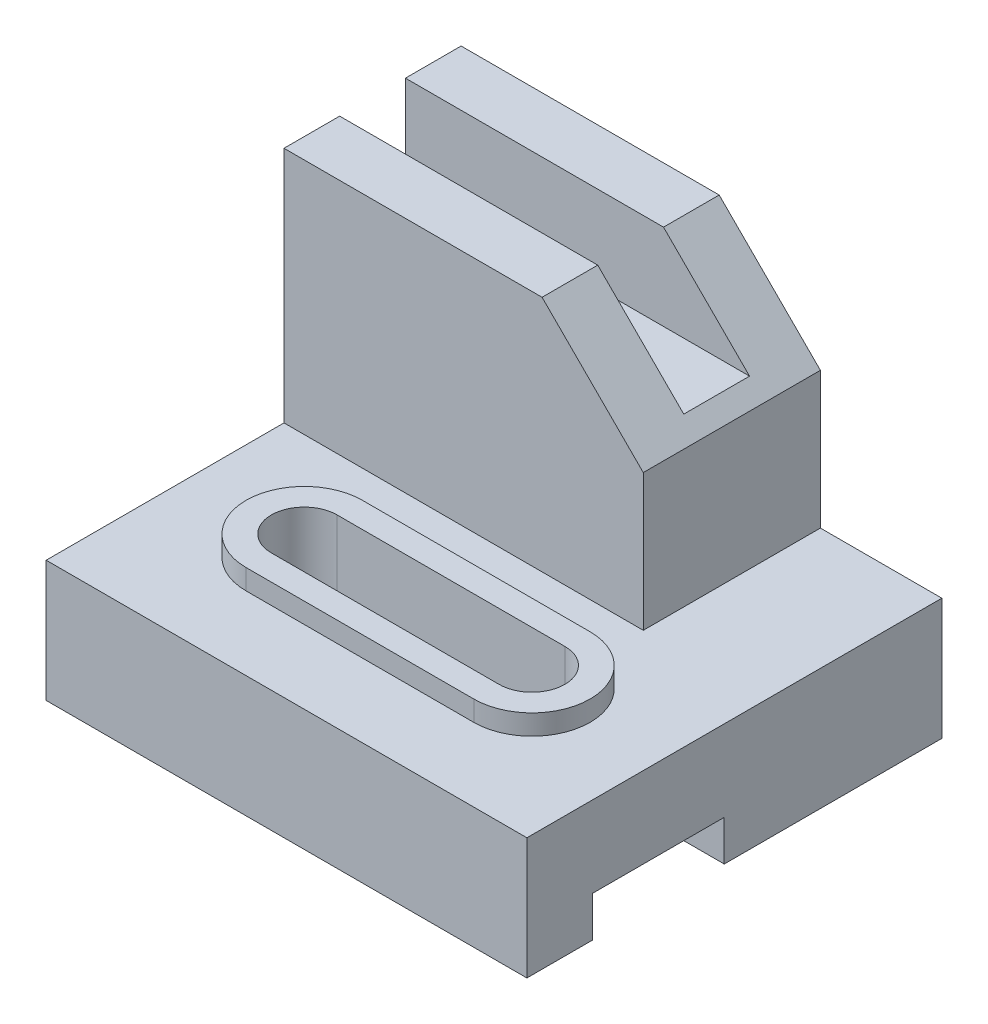
SolidWorks part; units mm, degrees
ref_plane "Front Plane" through (0, 0, 0) normal (0, 0, 1) x (1, 0, 0)
ref_plane "Top Plane" through (0, 0, 0) normal (0, 1, 0) x (1, 0, 0)
ref_plane "Right Plane" through (0, 0, 0) normal (1, 0, 0) x (0, 0, -1)
sketch "Sketch1" plane through (0, 0, 0) normal (0, 1, 0) x (1, 0, 0)
  line L0 (25, 26) -> (70, 26) construction
  line L1 (0, 0) -> (95, 0)
  line L2 (0, 0) -> (0, 82)
  line L3 (0, 82) -> (95, 82)
  line L4 (95, 0) -> (95, 82)
  line L5 (25, 37.5) -> (70, 37.5)
  line L6 (25, 14.5) -> (70, 14.5)
  line L7 (71, 82) -> (71, 47)
  line L8 (71, 47) -> (0, 47)
  line L9 (0, 71) -> (71, 71)
  line L10 (71, 58) -> (0, 58)
  line L11 (67.3875, 64.5) -> (76.8375, 64.5) construction
  line L12 (25, 32.5) -> (70, 32.5)
  line L13 (25, 19.5) -> (70, 19.5)
  arc A0 (25, 37.5) -> (25, 14.5) centre (25, 26) ccw
  arc A1 (70, 14.5) -> (70, 37.5) centre (70, 26) ccw
  arc A2 (70, 19.5) -> (70, 32.5) centre (70, 26) ccw
  arc A3 (25, 32.5) -> (25, 19.5) centre (25, 26) ccw
  point P7 (47.5, 26)
  point P21 (71, 64.5)
  dimension "D1" = 45
  dimension "D2" = 25
  dimension "D3" = 23
  dimension "D4" = 82
  dimension "D5" = 21
  dimension "D6" = 71
  dimension "D7" = 35
  dimension "D8" = 95
  dimension "D9" = 13
  dimension "D10" = 5
extrude "Boss-Extrude1" add sketch "Sketch1" along normal blind 24 contours L7 L8 L2 L1 L4 L3 A1 L6 A0 L5 region at (1.255, 0, -23.5)
extrude "Boss-Extrude2" add sketch "Sketch1<3>" along normal blind 28 contours L6 A1 L5 A0 A3 L12 A2 L13 region at (47.5, 0, -36.7822)
sketch "Sketch1<3>" plane through (0, 0, 0) normal (0, 1, 0) x (1, 0, 0) same geometry as "Sketch1"
extrude "Boss-Extrude3" add sketch "Sketch1<4>" along normal blind 71 contours L2 L9 L7 L3 | L7 L10 L2 L8 region at (35.5, 0, -52.5) region at (35.5, 0, -76.5)
sketch "Sketch1<4>" plane through (0, 0, 0) normal (0, 1, 0) x (1, 0, 0) same geometry as "Sketch1"
extrude "Boss-Extrude4" add sketch "Sketch1<5>" along normal blind 54 contours L10 L7 L9 L2 region at (35.5, 0, -64.5)
sketch "Sketch1<5>" plane through (0, 0, 0) normal (0, 1, 0) x (1, 0, 0) same geometry as "Sketch1"
sketch "Sketch2" plane through (95, 0, 0) normal (1, 0, 0) x (0, 0, -1)
  line L1 (13, 0) -> (39, 0)
  line L2 (13, 0) -> (13, 8)
  line L3 (13, 8) -> (39, 8)
  line L4 (39, 0) -> (39, 8)
  line L5 (0, 0) -> (82, 0) construction
  line L6 (26, 29.4325) -> (26, 22.1047) construction
  line L7 (14.5, 28) -> (14.5, 24) construction
  point P10 (0, 0)
  point P13 (0, 0)
  dimension "D1" = 26
  dimension "D2" = 8
  dimension "D3" = 11.5
extrude "Cut-Extrude1" cut sketch "Sketch2" against normal blind 96
chamfer "Chamfer1" distance 20 angle 45 1 edges at (71, 71, -76.5)
